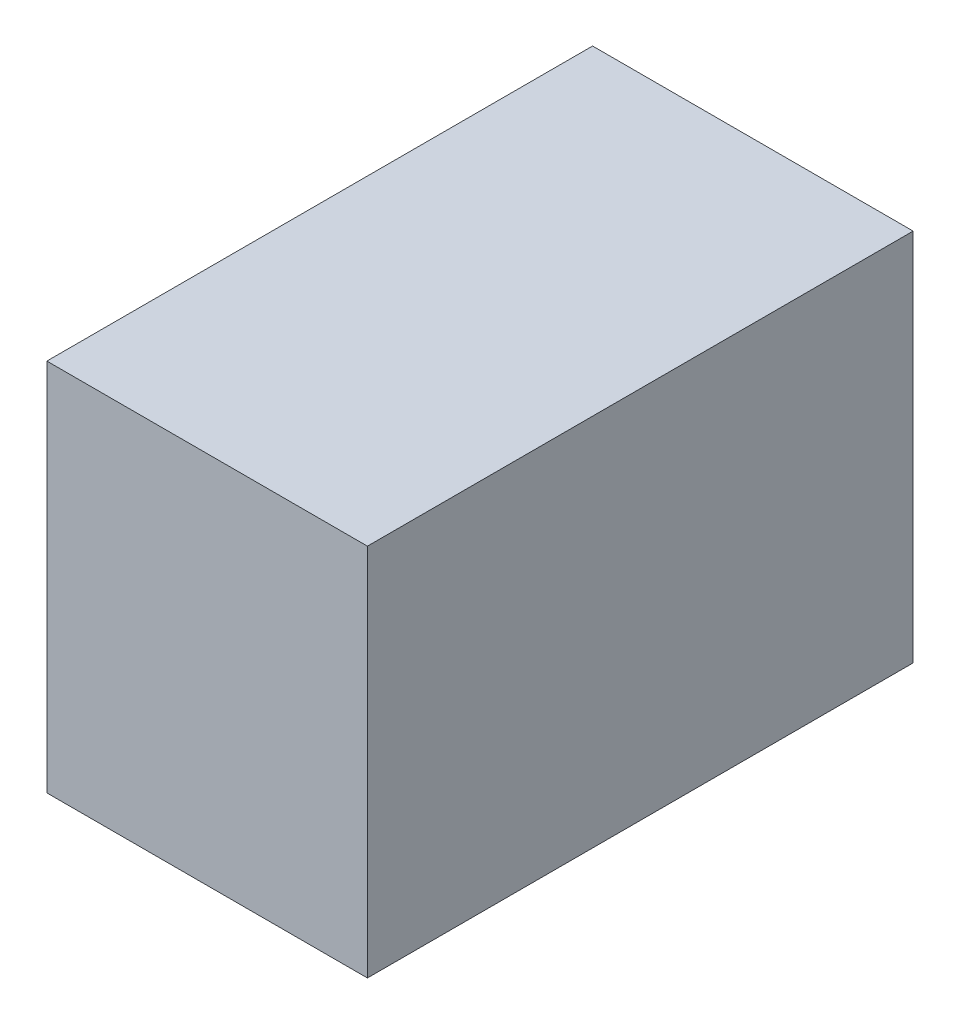
SolidWorks part; units mm, degrees
ref_plane "Front Plane" through (0, 0, 0) normal (0, 0, 1) x (1, 0, 0)
ref_plane "Top Plane" through (0, 0, 0) normal (0, 1, 0) x (1, 0, 0)
ref_plane "Right Plane" through (0, 0, 0) normal (1, 0, 0) x (0, 0, -1)
sketch "Sketch4" plane through (0, 0, 0) normal (1, 0, 0) x (0, 0, -1)
  line L1 (-15.875, 10.25) -> (15.875, 10.25)
  line L2 (-15.875, 10.25) -> (-15.875, -10.25)
  line L3 (-15.875, -10.25) -> (15.875, -10.25)
  line L4 (15.875, 10.25) -> (15.875, -10.25)
  line L5 (-15.875, 10.25) -> (15.875, -10.25) construction
  line L6 (-15.875, -10.25) -> (15.875, 10.25) construction
  point P0 (0, 0)
  dimension "D1" = 31.75
  dimension "D2" = 20.5
extrude "Boss-Extrude1" add sketch "Sketch4" along normal blind 19
shell "Shell1" thickness 2 removed face at (0, 0, 0) outward yes
sketch "Sketch5" plane through (0, 0, -17.875) normal (0, 0, -1) x (-1, 0, 0)
  line L0 (0, -12.25) -> (0, 12.25) construction
  line L1 (0, 10.25) -> (-12, 10.25)
  line L2 (-12, 10.25) -> (-12, -10.25)
  line L3 (-12, -10.25) -> (0, -10.25)
  line L4 (-21, 12.25) -> (0, 12.25) construction
  line L5 (-21, -12.25) -> (0, -12.25) construction
  line L6 (0, 10.25) -> (0, -10.25)
  dimension "D1" = 12
  dimension "D2" = 2
  dimension "D3" = 2
extrude "Cut-Extrude1" cut sketch "Sketch5" against normal up to surface (2 mm away) up to face at (9.5, 0, -15.875)
equation "\"terminalRad\"= 3mm"
equation "\"terminalLen\"= 10.5mm"
equation "\"threadlen\"=11"
